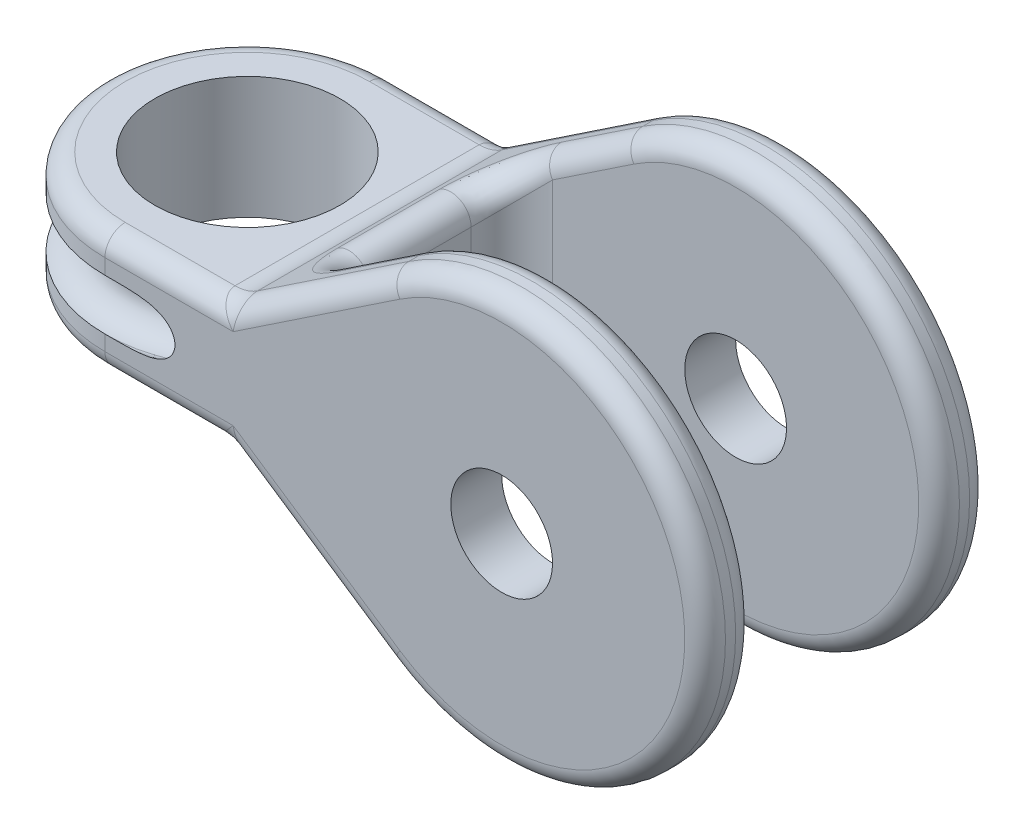
SolidWorks part; units mm, degrees
ref_plane "Front Plane" through (0, 0, 0) normal (0, 0, 1) x (1, 0, 0)
ref_plane "Top Plane" through (0, 0, 0) normal (0, 1, 0) x (1, 0, 0)
ref_plane "Right Plane" through (0, 0, 0) normal (1, 0, 0) x (0, 0, -1)
ref_plane "Front" through (0, 0, 4.5) normal (0, 0, 1) x (1, 0, 0)
ref_plane "Back" through (0, 0, -4.5) normal (0, 0, -1) x (-1, 0, 0)
sketch "Sketch8" plane through (0, 0, 4.5) normal (0, 0, 1) x (1, 0, 0)
  circle A0 centre (0, 0) radius 10
  circle A1 centre (0, 0) radius 2.5
  dimension "D1" = 20
  dimension "D2" = 5
extrude "Boss-Extrude3" add sketch "Sketch8" along normal blind 2.5
sketch "Sketch10" plane through (0, 0, -4.5) normal (0, 0, -1) x (-1, 0, 0)
  circle A0 centre (0, 0) radius 10
  circle A1 centre (0, 0) radius 2.5
  dimension "D1" = 20
  dimension "D2" = 5
extrude "Boss-Extrude4" add sketch "Sketch10" along normal blind 2.5 separate body
sketch "Sketch11" plane through (0, 0, 0) normal (0, 1, 0) x (1, 0, 0)
  line L0 (-38.7738, 0) -> (13.2618, 0) construction
  line L1 (-10, 7) -> (-10, -7) construction
  line L2 (-19.5, -7) -> (-13.5, -7)
  line L4 (-19.5, 7) -> (-13.5, 7)
  line L5 (-13.5, -7) -> (-13.5, 7)
  line L6 (-24.0555, -5.3148) -> (-13.5, 7) construction
  line L7 (-24.0555, 5.3148) -> (-13.5, -7) construction
  line L8 (-10, -7) -> (10, -7) construction
  arc A0 (-19.5, 7) -> (-19.5, -7) centre (-19.5, 0) ccw
  circle A1 centre (-19.5, 0) radius 4.55
  point P17 (-19.5, 0)
  dimension "D1" = 14
  dimension "D2" = 9.1
  dimension "D3" = 3.5
extrude "Boss-Extrude9" add sketch "Sketch11" along normal blind 3 and the other way blind 3 separate body contours L4 L5 L2 A0 | A1
sketch "Sketch12" plane through (0, 0, 0) normal (0, 1, 0) x (1, 0, 0)
  line L0 (-13.5, -7) -> (-10, -7)
  line L1 (-10, -7) -> (-10, 0)
  line L2 (-11, 0) -> (11, 0) construction
  line L3 (-10, 0) -> (-13.5, 0)
  line L4 (-13.5, -7) -> (-13.5, 7) construction
  line L5 (-13.5, 0) -> (-13.5, -7)
  point P0 (-13.5, -7)
  point P1 (-10, -7)
extrude "Boss-Extrude10" add sketch "Sketch12" along normal blind 3 and the other way blind 3
sketch "Sketch22" plane through (0, 0, 7) normal (0, 0, 1) x (1, 0, 0)
  line L0 (-19.5, 3) -> (-10, 3) construction
  line L1 (-10, 0) -> (-14.8775, 0) construction
  line L2 (-10, -3) -> (-10, 3) construction
  line L3 (-13.5, 3) -> (-5.5604, 8.3116)
  line L4 (-13.5, -3) -> (-5.5604, -8.3116)
  line L5 (-13.5, 3) -> (-13.5, -3)
  line L6 (-5.5604, 8.3116) -> (-5.5604, -8.3116)
  circle A0 centre (0, 0) radius 10 construction
  point P0 (-13.5, 3)
  point P9 (-13.5, -3)
  dimension "D1" = 3.5
sketch "Sketch14" plane through (0, 0, 7) normal (0, 0, 1) x (1, 0, 0)
  line L0 (-13.381, 2.0953) -> (-6.2511, 7.8054)
  line L1 (-13.381, -2.0953) -> (-6.2511, -7.8054)
  line L2 (-6.2511, 7.8054) -> (-6.2511, -7.8054)
  line L3 (-13.381, 2.0953) -> (-13.381, -2.0953)
  circle A0 centre (0, 0) radius 10 construction
  circle A1 centre (0, 0) radius 10 construction
  dimension "D1" = 3.5
extrude "Boss-Extrude12" add sketch "Sketch14" against normal through all
extrude "Boss-Extrude14" add sketch "Sketch22" against normal through all
sketch "Sketch16" plane through (0, 0, 0) normal (0, 1, 0) x (1, 0, 0)
  line L0 (-13.5, -7) -> (-13.5, 7) construction
  line L1 (-9, -4.5) -> (-2.7376, -4.5)
  line L2 (11.3013, 0) -> (-30.4765, 0) construction
  line L4 (-11, -2.5) -> (-11, 2.5)
  line L10 (-9, 4.5) -> (-2.7376, 4.5)
  line L11 (-2.7376, -4.5) -> (-2.7376, 4.5)
  line L12 (-11, -4.5) -> (-2.7376, 4.5) construction
  line L13 (-11, 4.5) -> (-2.7376, -4.5) construction
  arc A5 (-9, -4.5) -> (-11, -2.5) centre (-9, -2.5) cw
  arc A6 (-11, 2.5) -> (-9, 4.5) centre (-9, 2.5) cw
  point P2 (-11, 0)
  point P4 (-13.5, 0)
  dimension "D2" = 2
  dimension "D1" = 2.5
extrude "Cut-Extrude3" cut sketch "Sketch16" against normal through all and the other way through all
fillet "Fillet6" radius 1 6 edges at (10, 0, 7) (10, 0, -7) (-9.5302, -5.6558, 7) (-9.5302, 5.6558, 7) (-9.5302, 5.6558, -7) (-9.5302, -5.6558, -7)
sketch "Sketch21" plane through (0, 0, 0) normal (0, 0, 1) x (1, 0, 0)
  line L0 (-27.75, 0) -> (-28.174, 0) construction
  line L1 (-19.5, 6.0919) -> (-19.5, -5.6596) construction
  line L2 (-25.1454, 0) -> (-27.3, 0) construction
  line L3 (-26.5, 3) -> (-26.5, -3) construction
  arc A0 (-26.5, -1.25) -> (-26.5, 1.25) centre (-26.5, 0) ccw
  ellipse E0 centre (-26.5, 0) end of major axis (-26.5, 1.25) minor radius 0.8 (-26.5, 1.25) -> (-26.5, -1.25) ccw
  point P2 (-26.5, 0)
  dimension "D1" = 0.8
  dimension "D2" = 2.5
revolve "Cut-Revolve4" cut sketch "Sketch21" angle 360 about L1
fillet "Fillet7" radius 1 6 edges at (-15.6008, -3, -7) (-26.5, -3, 0) (-15.6008, -3, 7) (-15.6008, 3, -7) (-15.6008, 3, 7) (-26.5, 3, 0)
fillet "Fillet8" radius 2 6 edges at (-13.4111, -2.7071, 6.7071) (-13.4111, -2.7071, -6.7071) (-13.4111, 2.7071, 6.7071) (-13.4111, 2.7071, -6.7071) (-13.5, -3, 0) (-13.5, 3, 0)
fillet "Fillet9" radius 1 12 edges at (-10.4142, 5.0644, -3.9142) (-7.2802, 7.161, -4.5) (10, 0, -4.5) (-7.2802, -7.161, -4.5) (-10.4142, -5.0644, -3.9142) (-11, -4.6725, 0) (-10.4142, -5.0644, 3.9142) (-7.2802, -7.161, 4.5) (10, 0, 4.5) (-7.2802, 7.161, 4.5) (-10.4142, 5.0644, 3.9142) (-11, 4.6725, 0)
